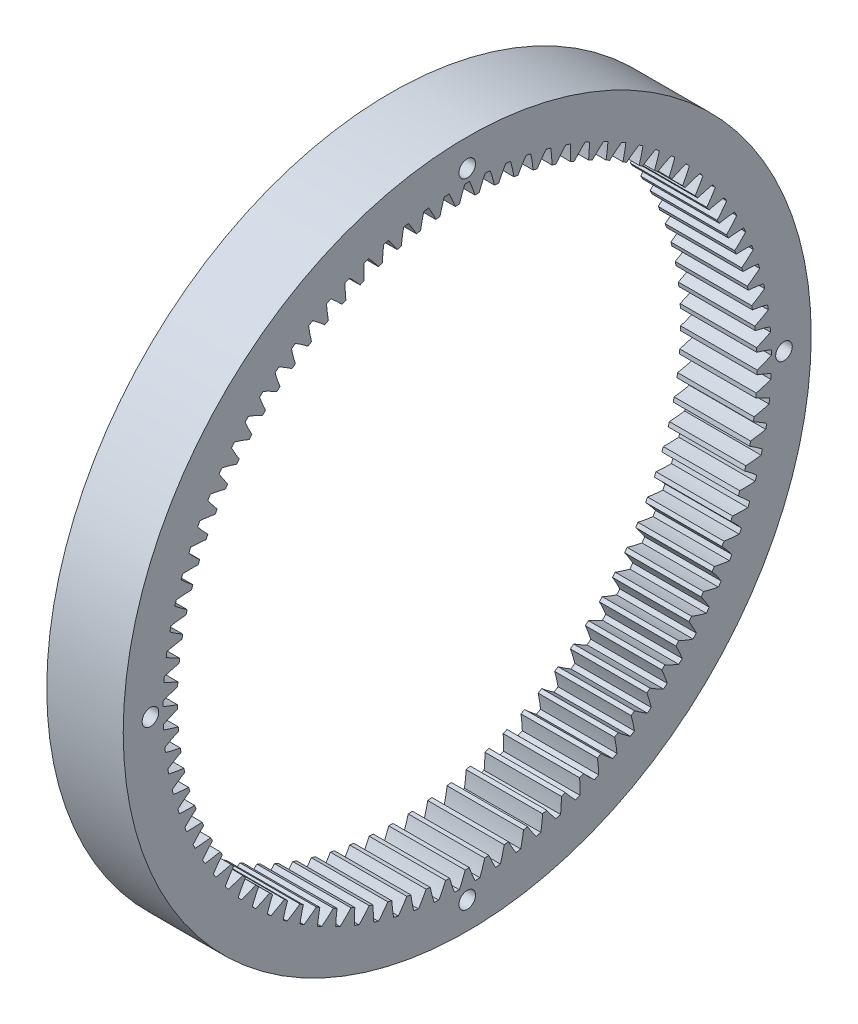
SolidWorks part; units mm, degrees
ref_plane "Plane1" through (0, 0, 0) normal (0, 0, 1) x (1, 0, 0)
ref_plane "Plane2" through (0, 0, 0) normal (0, 1, 0) x (1, 0, 0)
ref_plane "Plane3" through (0, 0, 0) normal (1, 0, 0) x (0, 0, -1)
sketch "HoldingSke" plane through (0, 0, 0) normal (0, 1, 0) x (1, 0, 0)
  line L0 (0, 0) -> (-0.0209, -0.3995)
  line L1 (-15, 0) -> (100, 0) construction
  line L2 (0, 0) -> (-2.1039, 2.3779)
  line L3 (0, 0) -> (-11.863, 4.5341)
  line L4 (0, 0) -> (-0.452, 8.6242)
  line L5 (0, 0) -> (-23.7986, -8.8762)
  line L6 (0, 0) -> (-10.5278, -7.1032)
  line L7 (-2.1039, 2.3779) -> (3.3635, 27.1825)
  line L8 (-76.2, 4.8779) -> (-54.61, 4.8779)
  line L9 (-71.009, 38.7566) -> (-53.1078, 45.2721)
  line L10 (-76.2, 71.12) -> (104.1128, 71.12)
  line L11 (0, 0) -> (-30, 0)
  line L12 (-76.2, 101.6) -> (-76.113, 101.6)
  line L13 (24.9733, 27.94) -> (52.9518, 28.4284)
  line L14 (24.9733, 27.94) -> (24.9743, 27.94)
  line L15 (24.9733, 27.94) -> (100.4006, 29.5858)
  circle A0 centre (0, 0) radius 50
  circle A1 centre (0, 0) radius 12.7
  circle A2 centre (0, 0) radius 12.7
  dimension "MHD" = 25.4
  dimension "Hub_dia" = 25.4
  dimension "Diameter" = 100
  dimension "Num_teeth" = 93
  dimension "Pitch" = 0.4
  dimension "Overall_len" = 25.4
  dimension "Show_teeth" = 93
  dimension "Thickness" = 12.7
  dimension "OAL" = 25.4001
  dimension "T_dim" = 21.59
  dimension "Ap" = 20
  dimension "H" = 19.05
  dimension "Pitch_radius" = 180.3128
  dimension "Width" = 30
  dimension "Backlash" = 0.087
  dimension "Addendum_fac" = 1
  dimension "Dedendum_fac" = 1.25
  dimension "Clearance_fac" = 0.25
  dimension "Dedendum_add" = 0.001
  dimension "Module" = 2.5
sketch "BasProSke" plane through (0, 0, 0) normal (0, 1, 0) x (1, 0, 0)
  line L0 (-10, 0) -> (60, 0) construction
  line L1 (0, 113.75) -> (0, 119.4014)
  line L2 (0, 113.75) -> (30, 113.75)
  line L3 (30, 113.75) -> (30, 119.4014)
  line L4 (30, 119.4014) -> (0, 119.4014)
  dimension "Thickness" = 30
  dimension "Diameter" = 238.8028
  dimension "Inside_diameter" = 227.5
revolve "Base-Revolve" add sketch "BasProSke" angle 360 about L0
sketch "TooCutSke" plane through (0, 0, 0) normal (1, 0, 0) x (0, 0, -1)
  line L3 (2.1809, 116.2295) -> (2.1809, 53.6633) construction
  line L4 (0, 0) -> (0, 59.563) construction
  line L5 (0, 0) -> (-2.3077, 68.2885) construction
  line L6 (-52.5279, 96.5964) -> (34.5007, 99.5374) construction
  circle A0 centre (0, 0) radius 116.25 construction
  circle A1 centre (0, 0) radius 119.376 construction
  circle A2 centre (0, 0) radius 98.3153 construction
  circle A3 centre (0, 0) radius 113.7246 construction
  arc A4 (3.0285, 113.6843) -> (0.949, 119.3722) centre (-52.5279, 96.5964) ccw
  arc A5 (3.0285, 113.6843) -> (-3.0285, 113.6843) centre (0, 0) ccw
  arc A6 (0.949, 119.3722) -> (-0.949, 119.3722) centre (0, 0) ccw
  arc A7 (-0.949, 119.3722) -> (-3.0285, 113.6843) centre (52.5279, 96.5964) ccw
  dimension "Pitch_dia" = 232.5
  dimension "Base_dia" = 196.6307
  dimension "Root_dia" = 238.752
  dimension "Overcut_dia" = 227.4492
  dimension "Flank_rad" = 58.125
  dimension "Half_ang" = 1.935
  dimension "Half_CT" = 2.1809
extrude "ToothCut" cut sketch "TooCutSke" along normal through all
fillet "Breaks" [suppressed] radius 0.25
fillet "RootFillets" [suppressed] radius 0.626
pattern_circular "TeethCuts" count 93 every 3.871 about axis through (-10, 0, 0) along (1, 0, 0) of "RootFillets", "Breaks", "ToothCut"
sketch "草圖2" plane through (0, 0, 0) normal (-1, 0, 0) x (0, 0, 1)
  line L0 (-124.305, 0) -> (150.1653, 0) construction
  line L1 (0, 146.5311) -> (0, -139.1781) construction
  line L9 (0, -124.305) -> (0, 150.1653) construction
  line L13 (124.305, 0) -> (-150.1653, 0) construction
  line L17 (0, 124.305) -> (0, -150.1653) construction
  circle A0 centre (0, 0) radius 119.4014 construction
  circle A1 centre (0, 0) radius 119.4014
  circle A3 centre (0, 0) radius 135
  circle A7 centre (0, 124.305) radius 3.25
  circle A8 centre (124.305, 0) radius 3.25
  circle A9 centre (0, -124.305) radius 3.25
  circle A10 centre (-124.305, 0) radius 3.25
  point P29 (0, 0)
  point P36 (0, 0)
  dimension "D2" = 4
  dimension "D5" = 6.5
  dimension "D1" = 270
  dimension "D3" = 248.61
  dimension "D4" = 4
extrude "填料-伸長1" add sketch "草圖2" against normal up to surface (30 mm away) up to face at (30, 0, 119.4014)
equation "' \"Module@HoldingSke\" = 6.35"
equation "' \"Num_teeth@HoldingSke\" = 24"
equation "' \"Ap@HoldingSke\" =  14.5"
equation "' \"Ap@HoldingSke\" = 14.5"
equation "' \"Width@HoldingSke\" = 12"
equation "' \"Diameter@HoldingSke\" = 8 * 25.4"
equation "' \"Show_teeth@HoldingSke\" = 100"
equation "' \"Backlash@HoldingSke\" = 0.009 * 25.4"
equation "' \"Addendum_fac@HoldingSke\" = 1.0"
equation "' \"Dedendum_fac@HoldingSke\" = 1.25"
equation "' \"Dedendum_add@HoldingSke\" = 0.00005 * 25.4"
equation "' \"Clearance_fac@HoldingSke\" = 0.25"
equation "\"Pitch@HoldingSke\" = 1 / \"Module@HoldingSke\" "
equation "\"Overcut_dia@TooCutSke\" = (\"Num_teeth@HoldingSke\" - 2 * \"Addendum_fac@HoldingSke\") / \"Pitch@HoldingSke\" - 0.002 * 25.4"
equation "\"Pitch_dia@TooCutSke\" = \"Num_teeth@HoldingSke\" / \"Pitch@HoldingSke\""
equation "\"Base_dia@TooCutSke\" = \"Num_teeth@HoldingSke\" / \"Pitch@HoldingSke\" * cos((\"Ap@HoldingSke\"  * 3.14159265 / 180)) * 0.90"
equation "\"Root_dia@TooCutSke\" = \"Num_teeth@HoldingSke\"  / \"Pitch@HoldingSke\" + 2 *  \"Dedendum_fac@HoldingSke\"/ \"Pitch@HoldingSke\" + \"Dedendum_add@HoldingSke\" * 2"
equation "\"Half_ang@TooCutSke\" = 180 / \"Num_teeth@HoldingSke\""
equation "\"Half_CT@TooCutSke\" = \"Num_teeth@HoldingSke\" / \"Pitch@HoldingSke\" * sin((3.14159265 / 2 / \"Num_teeth@HoldingSke\")) / 2 + 10 * \"Backlash@HoldingSke\" / 4"
equation "\"Flank_rad@TooCutSke\" = \"Num_teeth@HoldingSke\" / \"Pitch@HoldingSke\" / 4"
equation "\"Radius@RootFillets\"= \"Clearance_fac@HoldingSke\" / \"Pitch@HoldingSke\" + \"Dedendum_add@HoldingSke\""
equation "\"Break_rad@Breaks\" = 0.02 / \"Pitch@HoldingSke\" * 5"
equation "\"Num_teeth@TeethCuts\" = int( \"Show_teeth@HoldingSke\" ) + 1"
equation "\"Num_teeth@TeethCuts\" = ((sgn( \"Num_teeth@TeethCuts\" - \"Num_teeth@HoldingSke\" )-1)*( \"Num_teeth@TeethCuts\" - \"Num_teeth@HoldingSke\" ))/-2+ \"Num_teeth@HoldingSke\""
equation "\"Num_teeth@TeethCuts\" = ((sgn( \"Num_teeth@TeethCuts\" - 2.0)+1)*( \"Num_teeth@TeethCuts\" - 2.0))/2 +2.0"
equation "\"Angle@TeethCuts\" = 360.0 / \"Num_teeth@HoldingSke\""
equation "\"Diameter@BasProSke\" = \"Num_teeth@HoldingSke\"  / \"Pitch@HoldingSke\" + 2 *  \"Dedendum_fac@HoldingSke\"/ \"Pitch@HoldingSke\" + \"Dedendum_add@HoldingSke\" * 2 + 0.002 * 25.4"
equation "\"Diameter@BasProSke\" = ((sgn( \"Diameter@BasProSke\"  - \"Diameter@HoldingSke\" )+1)*( \"Diameter@BasProSke\"  - \"Diameter@HoldingSke\" ))/2 + \"Diameter@HoldingSke\""
equation "\"Inside_diameter@BasProSke\" =  (\"Num_teeth@HoldingSke\" - 2 * \"Addendum_fac@HoldingSke\") / \"Pitch@HoldingSke\" "
equation "\"Thickness@BasProSke\"  = \"Width@HoldingSke\""
